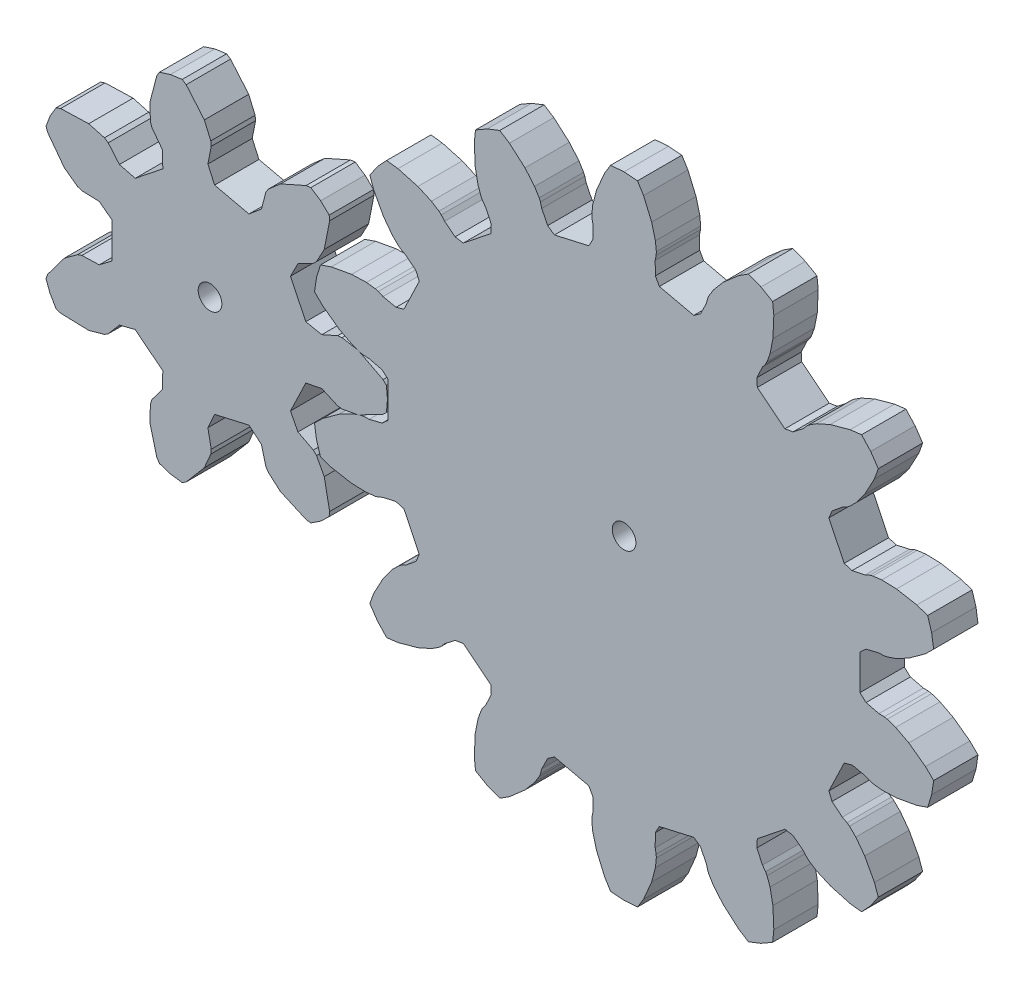
SolidWorks part; units mm, degrees
ref_plane "Front Plane" through (0, 0, 0) normal (0, 0, 1) x (1, 0, 0)
ref_plane "Top Plane" through (0, 0, 0) normal (0, 1, 0) x (1, 0, 0)
ref_plane "Right Plane" through (0, 0, 0) normal (1, 0, 0) x (0, 0, -1)
sketch "Model" plane through (0, 0, 0) normal (0, 0, 1) x (1, 0, 0)
  line L0 (10.824, -15.5893) -> (11.8775, -14.8939)
  line L1 (11.8775, -14.8939) -> (12.7899, -14.0216)
  line L2 (12.7899, -14.0216) -> (12.8434, -13.5144)
  line L3 (12.8434, -13.5144) -> (12.2623, -10.5576)
  line L4 (12.2623, -10.5576) -> (11.4342, -9.0171)
  line L5 (11.4342, -9.0171) -> (11.0892, -8.677)
  line L6 (11.0892, -8.677) -> (9.4401, -7.8202)
  line L7 (9.4401, -7.8202) -> (8.6391, -6.2612)
  line L8 (8.6391, -6.2612) -> (10.2816, -2.8505)
  line L9 (10.2816, -2.8505) -> (11.9999, -2.5047)
  line L10 (11.9999, -2.5047) -> (13.698, -3.2599)
  line L11 (13.698, -3.2599) -> (14.179, -3.3175)
  line L12 (14.179, -3.3175) -> (15.8632, -3.0111)
  line L13 (15.8632, -3.0111) -> (15.2951, -3.2054)
  line L14 (15.2951, -3.2054) -> (13.8858, -3.9376)
  line L15 (13.8858, -3.9376) -> (12.0928, -5.2415)
  line L16 (12.0928, -5.2415) -> (11.2168, -6.1052)
  line L17 (11.2168, -6.1052) -> (11.4324, -7.536)
  line L18 (11.4324, -7.536) -> (11.8589, -8.9187)
  line L19 (11.8589, -8.9187) -> (13.023, -9.3169)
  line L20 (13.023, -9.3169) -> (15.2041, -9.7136)
  line L21 (15.2041, -9.7136) -> (16.7916, -9.7618)
  line L22 (16.7916, -9.7618) -> (17.7443, -9.6477)
  line L23 (17.7443, -9.6477) -> (18.0633, -9.5598)
  line L24 (18.0633, -9.5598) -> (18.5734, -9.3329)
  line L25 (18.5734, -9.3329) -> (19.9687, -9.0348)
  line L26 (19.9687, -9.0348) -> (20.819, -9.2793)
  line L27 (20.819, -9.2793) -> (22.4615, -12.6899)
  line L28 (22.4615, -12.6899) -> (22.1225, -13.5071)
  line L29 (22.1225, -13.5071) -> (21.0194, -14.4122)
  line L30 (21.0194, -14.4122) -> (20.524, -14.6696)
  line L31 (20.524, -14.6696) -> (20.2564, -14.8641)
  line L32 (20.2564, -14.8641) -> (19.5731, -15.5378)
  line L33 (19.5731, -15.5378) -> (18.621, -16.809)
  line L34 (18.621, -16.809) -> (17.5714, -18.7617)
  line L35 (17.5714, -18.7617) -> (17.1569, -19.92)
  line L36 (17.1569, -19.92) -> (17.972, -21.1155)
  line L37 (17.972, -21.1155) -> (18.9562, -22.1762)
  line L38 (18.9562, -22.1762) -> (20.1777, -22.0299)
  line L39 (20.1777, -22.0299) -> (22.3149, -21.441)
  line L40 (22.3149, -21.441) -> (23.7661, -20.7956)
  line L41 (23.7661, -20.7956) -> (24.575, -20.2794)
  line L42 (24.575, -20.2794) -> (24.8242, -20.0619)
  line L43 (24.8242, -20.0619) -> (25.1854, -19.6361)
  line L44 (25.1854, -19.6361) -> (26.3132, -18.7621)
  line L45 (26.3132, -18.7621) -> (27.1854, -18.6134)
  line L46 (27.1854, -18.6134) -> (30.145, -20.9737)
  line L47 (30.145, -20.9737) -> (30.1941, -21.8571)
  line L48 (30.1941, -21.8571) -> (29.593, -23.151)
  line L49 (29.593, -23.151) -> (29.2583, -23.5979)
  line L50 (29.2583, -23.5979) -> (29.1016, -23.8893)
  line L51 (29.1016, -23.8893) -> (28.7783, -24.7928)
  line L52 (28.7783, -24.7928) -> (28.4721, -26.3512)
  line L53 (28.4721, -26.3512) -> (28.3736, -28.5659)
  line L54 (28.3736, -28.5659) -> (28.5027, -29.7893)
  line L55 (28.5027, -29.7893) -> (29.7558, -30.5128)
  line L56 (29.7558, -30.5128) -> (31.1028, -31.0414)
  line L57 (31.1028, -31.0414) -> (32.1398, -30.3796)
  line L58 (32.1398, -30.3796) -> (33.8099, -28.9217)
  line L59 (33.8099, -28.9217) -> (34.8374, -27.7106)
  line L60 (34.8374, -27.7106) -> (35.3421, -26.8946)
  line L61 (35.3421, -26.8946) -> (35.4723, -26.5904)
  line L62 (35.4723, -26.5904) -> (35.613, -26.0501)
  line L63 (35.613, -26.0501) -> (36.2499, -24.7734)
  line L64 (36.2499, -24.7734) -> (36.9712, -24.261)
  line L65 (36.9712, -24.261) -> (40.6618, -25.1033)
  line L66 (40.6618, -25.1033) -> (41.0893, -25.8779)
  line L67 (41.0893, -25.8779) -> (41.1092, -27.3046)
  line L68 (41.1092, -27.3046) -> (41.0015, -27.8524)
  line L69 (41.0015, -27.8524) -> (40.9868, -28.183)
  line L70 (40.9868, -28.183) -> (41.0875, -29.1372)
  line L71 (41.0875, -29.1372) -> (41.4877, -30.6741)
  line L72 (41.4877, -30.6741) -> (42.3599, -32.7123)
  line L73 (42.3599, -32.7123) -> (43.0071, -33.7585)
  line L74 (43.0071, -33.7585) -> (44.45, -33.8667)
  line L75 (44.45, -33.8667) -> (45.8929, -33.7585)
  line L76 (45.8929, -33.7585) -> (46.5401, -32.7123)
  line L77 (46.5401, -32.7123) -> (47.4123, -30.6741)
  line L78 (47.4123, -30.6741) -> (47.8125, -29.1372)
  line L79 (47.8125, -29.1372) -> (47.9132, -28.183)
  line L80 (47.9132, -28.183) -> (47.8985, -27.8524)
  line L81 (47.8985, -27.8524) -> (47.7908, -27.3046)
  line L82 (47.7908, -27.3046) -> (47.8107, -25.8779)
  line L83 (47.8107, -25.8779) -> (48.2382, -25.1033)
  line L84 (48.2382, -25.1033) -> (51.9288, -24.261)
  line L85 (51.9288, -24.261) -> (52.6501, -24.7734)
  line L86 (52.6501, -24.7734) -> (53.287, -26.0501)
  line L87 (53.287, -26.0501) -> (53.4277, -26.5904)
  line L88 (53.4277, -26.5904) -> (53.5579, -26.8946)
  line L89 (53.5579, -26.8946) -> (54.0626, -27.7106)
  line L90 (54.0626, -27.7106) -> (55.0901, -28.9217)
  line L91 (55.0901, -28.9217) -> (56.7602, -30.3796)
  line L92 (56.7602, -30.3796) -> (57.7972, -31.0414)
  line L93 (57.7972, -31.0414) -> (59.1442, -30.5128)
  line L94 (59.1442, -30.5128) -> (60.3973, -29.7893)
  line L95 (60.3973, -29.7893) -> (60.5264, -28.5659)
  line L96 (60.5264, -28.5659) -> (60.4279, -26.3512)
  line L97 (60.4279, -26.3512) -> (60.1217, -24.7928)
  line L98 (60.1217, -24.7928) -> (59.7984, -23.8893)
  line L99 (59.7984, -23.8893) -> (59.6417, -23.5979)
  line L100 (59.6417, -23.5979) -> (59.307, -23.151)
  line L101 (59.307, -23.151) -> (58.7059, -21.8571)
  line L102 (58.7059, -21.8571) -> (58.755, -20.9737)
  line L103 (58.755, -20.9737) -> (61.7146, -18.6134)
  line L104 (61.7146, -18.6134) -> (62.5868, -18.7621)
  line L105 (62.5868, -18.7621) -> (63.7146, -19.6361)
  line L106 (63.7146, -19.6361) -> (64.0758, -20.0619)
  line L107 (64.0758, -20.0619) -> (64.325, -20.2794)
  line L108 (64.325, -20.2794) -> (65.1339, -20.7956)
  line L109 (65.1339, -20.7956) -> (66.5851, -21.441)
  line L110 (66.5851, -21.441) -> (68.7223, -22.0299)
  line L111 (68.7223, -22.0299) -> (69.9438, -22.1762)
  line L112 (69.9438, -22.1762) -> (70.928, -21.1155)
  line L113 (70.928, -21.1155) -> (71.7431, -19.92)
  line L114 (71.7431, -19.92) -> (71.3286, -18.7617)
  line L115 (71.3286, -18.7617) -> (70.279, -16.809)
  line L116 (70.279, -16.809) -> (69.3269, -15.5378)
  line L117 (69.3269, -15.5378) -> (68.6436, -14.8641)
  line L118 (68.6436, -14.8641) -> (68.376, -14.6696)
  line L119 (68.376, -14.6696) -> (67.8806, -14.4122)
  line L120 (67.8806, -14.4122) -> (66.7775, -13.5071)
  line L121 (66.7775, -13.5071) -> (66.4385, -12.6899)
  line L122 (66.4385, -12.6899) -> (68.081, -9.2793)
  line L123 (68.081, -9.2793) -> (68.9313, -9.0348)
  line L124 (68.9313, -9.0348) -> (70.3266, -9.3329)
  line L125 (70.3266, -9.3329) -> (70.8367, -9.5598)
  line L126 (70.8367, -9.5598) -> (71.1557, -9.6477)
  line L127 (71.1557, -9.6477) -> (72.1084, -9.7618)
  line L128 (72.1084, -9.7618) -> (73.6959, -9.7136)
  line L129 (73.6959, -9.7136) -> (75.877, -9.3169)
  line L130 (75.877, -9.3169) -> (77.0411, -8.9187)
  line L131 (77.0411, -8.9187) -> (77.4676, -7.536)
  line L132 (77.4676, -7.536) -> (77.6832, -6.1052)
  line L133 (77.6832, -6.1052) -> (76.8072, -5.2415)
  line L134 (76.8072, -5.2415) -> (75.0142, -3.9376)
  line L135 (75.0142, -3.9376) -> (73.6049, -3.2054)
  line L136 (73.6049, -3.2054) -> (72.697, -2.8949)
  line L137 (72.697, -2.8949) -> (72.3715, -2.8357)
  line L138 (72.3715, -2.8357) -> (71.8134, -2.8188)
  line L139 (71.8134, -2.8188) -> (70.4269, -2.482)
  line L140 (70.4269, -2.482) -> (69.7669, -1.8928)
  line L141 (69.7669, -1.8928) -> (69.7669, 1.8928)
  line L142 (69.7669, 1.8928) -> (70.4269, 2.482)
  line L143 (70.4269, 2.482) -> (71.8134, 2.8188)
  line L144 (71.8134, 2.8188) -> (72.3715, 2.8357)
  line L145 (72.3715, 2.8357) -> (72.697, 2.8949)
  line L146 (72.697, 2.8949) -> (73.6049, 3.2054)
  line L147 (73.6049, 3.2054) -> (75.0142, 3.9376)
  line L148 (75.0142, 3.9376) -> (76.8072, 5.2415)
  line L149 (76.8072, 5.2415) -> (77.6832, 6.1052)
  line L150 (77.6832, 6.1052) -> (77.4676, 7.536)
  line L151 (77.4676, 7.536) -> (77.0411, 8.9187)
  line L152 (77.0411, 8.9187) -> (75.877, 9.3169)
  line L153 (75.877, 9.3169) -> (73.6959, 9.7136)
  line L154 (73.6959, 9.7136) -> (72.1084, 9.7618)
  line L155 (72.1084, 9.7618) -> (71.1557, 9.6477)
  line L156 (71.1557, 9.6477) -> (70.8367, 9.5598)
  line L157 (70.8367, 9.5598) -> (70.3266, 9.3329)
  line L158 (70.3266, 9.3329) -> (68.9313, 9.0348)
  line L159 (68.9313, 9.0348) -> (68.081, 9.2793)
  line L160 (68.081, 9.2793) -> (66.4385, 12.6899)
  line L161 (66.4385, 12.6899) -> (66.7775, 13.5071)
  line L162 (66.7775, 13.5071) -> (67.8806, 14.4122)
  line L163 (67.8806, 14.4122) -> (68.376, 14.6696)
  line L164 (68.376, 14.6696) -> (68.6436, 14.8641)
  line L165 (68.6436, 14.8641) -> (69.3269, 15.5378)
  line L166 (69.3269, 15.5378) -> (70.279, 16.809)
  line L167 (70.279, 16.809) -> (71.3286, 18.7617)
  line L168 (71.3286, 18.7617) -> (71.7431, 19.92)
  line L169 (71.7431, 19.92) -> (70.928, 21.1155)
  line L170 (70.928, 21.1155) -> (69.9438, 22.1762)
  line L171 (69.9438, 22.1762) -> (68.7223, 22.0299)
  line L172 (68.7223, 22.0299) -> (66.5851, 21.441)
  line L173 (66.5851, 21.441) -> (65.1339, 20.7956)
  line L174 (65.1339, 20.7956) -> (64.325, 20.2794)
  line L175 (64.325, 20.2794) -> (64.0758, 20.0619)
  line L176 (64.0758, 20.0619) -> (63.7146, 19.6361)
  line L177 (63.7146, 19.6361) -> (62.5868, 18.7621)
  line L178 (62.5868, 18.7621) -> (61.7146, 18.6134)
  line L179 (61.7146, 18.6134) -> (58.755, 20.9737)
  line L180 (58.755, 20.9737) -> (58.7059, 21.8571)
  line L181 (58.7059, 21.8571) -> (59.307, 23.151)
  line L182 (59.307, 23.151) -> (59.6417, 23.5979)
  line L183 (59.6417, 23.5979) -> (59.7984, 23.8893)
  line L184 (59.7984, 23.8893) -> (60.1217, 24.7928)
  line L185 (60.1217, 24.7928) -> (60.4279, 26.3512)
  line L186 (60.4279, 26.3512) -> (60.5264, 28.5659)
  line L187 (60.5264, 28.5659) -> (60.3973, 29.7893)
  line L188 (60.3973, 29.7893) -> (59.1442, 30.5128)
  line L189 (59.1442, 30.5128) -> (57.7972, 31.0414)
  line L190 (57.7972, 31.0414) -> (56.7602, 30.3796)
  line L191 (56.7602, 30.3796) -> (55.0901, 28.9217)
  line L192 (55.0901, 28.9217) -> (54.0626, 27.7106)
  line L193 (54.0626, 27.7106) -> (53.5579, 26.8946)
  line L194 (53.5579, 26.8946) -> (53.4277, 26.5904)
  line L195 (53.4277, 26.5904) -> (53.287, 26.0501)
  line L196 (53.287, 26.0501) -> (52.6501, 24.7734)
  line L197 (52.6501, 24.7734) -> (51.9288, 24.261)
  line L198 (51.9288, 24.261) -> (48.2382, 25.1033)
  line L199 (48.2382, 25.1033) -> (47.8107, 25.8779)
  line L200 (47.8107, 25.8779) -> (47.7908, 27.3046)
  line L201 (47.7908, 27.3046) -> (47.8985, 27.8524)
  line L202 (47.8985, 27.8524) -> (47.9132, 28.183)
  line L203 (47.9132, 28.183) -> (47.8125, 29.1372)
  line L204 (47.8125, 29.1372) -> (47.4123, 30.6741)
  line L205 (47.4123, 30.6741) -> (46.5401, 32.7123)
  line L206 (46.5401, 32.7123) -> (45.8929, 33.7585)
  line L207 (45.8929, 33.7585) -> (44.45, 33.8667)
  line L208 (44.45, 33.8667) -> (43.0071, 33.7585)
  line L209 (43.0071, 33.7585) -> (42.3599, 32.7123)
  line L210 (42.3599, 32.7123) -> (41.4877, 30.6741)
  line L211 (41.4877, 30.6741) -> (41.0875, 29.1372)
  line L212 (41.0875, 29.1372) -> (40.9868, 28.183)
  line L213 (40.9868, 28.183) -> (41.0015, 27.8524)
  line L214 (41.0015, 27.8524) -> (41.1092, 27.3046)
  line L215 (41.1092, 27.3046) -> (41.0893, 25.8779)
  line L216 (41.0893, 25.8779) -> (40.6618, 25.1033)
  line L217 (40.6618, 25.1033) -> (36.9712, 24.261)
  line L218 (36.9712, 24.261) -> (36.2499, 24.7734)
  line L219 (36.2499, 24.7734) -> (35.613, 26.0501)
  line L220 (35.613, 26.0501) -> (35.4723, 26.5904)
  line L221 (35.4723, 26.5904) -> (35.3421, 26.8946)
  line L222 (35.3421, 26.8946) -> (34.8374, 27.7106)
  line L223 (34.8374, 27.7106) -> (33.8099, 28.9217)
  line L224 (33.8099, 28.9217) -> (32.1398, 30.3796)
  line L225 (32.1398, 30.3796) -> (31.1028, 31.0414)
  line L226 (31.1028, 31.0414) -> (29.7558, 30.5128)
  line L227 (29.7558, 30.5128) -> (28.5027, 29.7893)
  line L228 (28.5027, 29.7893) -> (28.3736, 28.5659)
  line L229 (28.3736, 28.5659) -> (28.4721, 26.3512)
  line L230 (28.4721, 26.3512) -> (28.7783, 24.7928)
  line L231 (28.7783, 24.7928) -> (29.1016, 23.8893)
  line L232 (29.1016, 23.8893) -> (29.2583, 23.5979)
  line L233 (29.2583, 23.5979) -> (29.593, 23.151)
  line L234 (29.593, 23.151) -> (30.1941, 21.8571)
  line L235 (30.1941, 21.8571) -> (30.145, 20.9737)
  line L236 (30.145, 20.9737) -> (27.1854, 18.6134)
  line L237 (27.1854, 18.6134) -> (26.3132, 18.7621)
  line L238 (26.3132, 18.7621) -> (25.1854, 19.6361)
  line L239 (25.1854, 19.6361) -> (24.8242, 20.0619)
  line L240 (24.8242, 20.0619) -> (24.575, 20.2794)
  line L241 (24.575, 20.2794) -> (23.7661, 20.7956)
  line L242 (23.7661, 20.7956) -> (22.3149, 21.441)
  line L243 (22.3149, 21.441) -> (20.1777, 22.0299)
  line L244 (20.1777, 22.0299) -> (18.9562, 22.1762)
  line L245 (18.9562, 22.1762) -> (17.972, 21.1155)
  line L246 (17.972, 21.1155) -> (17.1569, 19.92)
  line L247 (17.1569, 19.92) -> (17.5714, 18.7617)
  line L248 (17.5714, 18.7617) -> (18.621, 16.809)
  line L249 (18.621, 16.809) -> (19.5731, 15.5378)
  line L250 (19.5731, 15.5378) -> (20.2564, 14.8641)
  line L251 (20.2564, 14.8641) -> (20.524, 14.6696)
  line L252 (20.524, 14.6696) -> (21.0194, 14.4122)
  line L253 (21.0194, 14.4122) -> (22.1225, 13.5071)
  line L254 (22.1225, 13.5071) -> (22.4615, 12.6899)
  line L255 (22.4615, 12.6899) -> (20.819, 9.2793)
  line L256 (20.819, 9.2793) -> (19.9687, 9.0348)
  line L257 (19.9687, 9.0348) -> (18.5734, 9.3329)
  line L258 (18.5734, 9.3329) -> (18.0633, 9.5598)
  line L259 (18.0633, 9.5598) -> (17.7443, 9.6477)
  line L260 (17.7443, 9.6477) -> (16.7916, 9.7618)
  line L261 (16.7916, 9.7618) -> (15.2041, 9.7136)
  line L262 (15.2041, 9.7136) -> (13.023, 9.3169)
  line L263 (13.023, 9.3169) -> (11.8589, 8.9187)
  line L264 (11.8589, 8.9187) -> (11.4324, 7.536)
  line L265 (11.4324, 7.536) -> (11.2168, 6.1052)
  line L266 (11.2168, 6.1052) -> (12.0928, 5.2415)
  line L267 (12.0928, 5.2415) -> (13.8858, 3.9376)
  line L268 (13.8858, 3.9376) -> (15.2951, 3.2054)
  line L269 (15.2951, 3.2054) -> (15.8632, 3.0111)
  line L270 (15.8632, 3.0111) -> (14.179, 3.3175)
  line L271 (14.179, 3.3175) -> (13.698, 3.2599)
  line L272 (13.698, 3.2599) -> (11.9999, 2.5047)
  line L273 (11.9999, 2.5047) -> (10.2816, 2.8505)
  line L274 (10.2816, 2.8505) -> (8.6391, 6.2612)
  line L275 (8.6391, 6.2612) -> (9.4401, 7.8202)
  line L276 (9.4401, 7.8202) -> (11.0892, 8.677)
  line L277 (11.0892, 8.677) -> (11.4342, 9.0171)
  line L278 (11.4342, 9.0171) -> (12.2623, 10.5576)
  line L279 (12.2623, 10.5576) -> (12.8434, 13.5144)
  line L280 (12.8434, 13.5144) -> (12.7899, 14.0216)
  line L281 (12.7899, 14.0216) -> (11.8775, 14.8939)
  line L282 (11.8775, 14.8939) -> (10.824, 15.5893)
  line L283 (10.824, 15.5893) -> (10.3177, 15.5286)
  line L284 (10.3177, 15.5286) -> (7.5643, 14.3042)
  line L285 (7.5643, 14.3042) -> (6.2467, 13.154)
  line L286 (6.2467, 13.154) -> (5.9919, 12.742)
  line L287 (5.9919, 12.742) -> (5.5235, 10.9436)
  line L288 (5.5235, 10.9436) -> (4.1818, 9.8158)
  line L289 (4.1818, 9.8158) -> (0.4912, 10.6581)
  line L290 (0.4912, 10.6581) -> (-0.2283, 12.2564)
  line L291 (-0.2283, 12.2564) -> (0.1301, 14.0799)
  line L292 (0.1301, 14.0799) -> (0.0792, 14.5617)
  line L293 (0.0792, 14.5617) -> (-0.6088, 16.1696)
  line L294 (-0.6088, 16.1696) -> (-2.5583, 18.4675)
  line L295 (-2.5583, 18.4675) -> (-2.9881, 18.7418)
  line L296 (-2.9881, 18.7418) -> (-4.239, 18.5724)
  line L297 (-4.239, 18.5724) -> (-5.4396, 18.1823)
  line L298 (-5.4396, 18.1823) -> (-5.7078, 17.7486)
  line L299 (-5.7078, 17.7486) -> (-6.4672, 14.8325)
  line L300 (-6.4672, 14.8325) -> (-6.3895, 13.0853)
  line L301 (-6.3895, 13.0853) -> (-6.2262, 12.6291)
  line L302 (-6.2262, 12.6291) -> (-5.1122, 11.1417)
  line L303 (-5.1122, 11.1417) -> (-5.067, 9.3895)
  line L304 (-5.067, 9.3895) -> (-8.0266, 7.0293)
  line L305 (-8.0266, 7.0293) -> (-9.7248, 7.4633)
  line L306 (-9.7248, 7.4633) -> (-10.927, 8.8804)
  line L307 (-10.927, 8.8804) -> (-11.3354, 9.141)
  line L308 (-11.3354, 9.141) -> (-13.0215, 9.6056)
  line L309 (-13.0215, 9.6056) -> (-16.0335, 9.5141)
  line L310 (-16.0335, 9.5141) -> (-16.516, 9.3491)
  line L311 (-16.516, 9.3491) -> (-17.1635, 8.2655)
  line L312 (-17.1635, 8.2655) -> (-17.607, 7.0837)
  line L313 (-17.607, 7.0837) -> (-17.4352, 6.6035)
  line L314 (-17.4352, 6.6035) -> (-15.6287, 4.1916)
  line L315 (-15.6287, 4.1916) -> (-14.2142, 3.163)
  line L316 (-14.2142, 3.163) -> (-13.7559, 3.0063)
  line L317 (-13.7559, 3.0063) -> (-11.8983, 2.9499)
  line L318 (-11.8983, 2.9499) -> (-10.5002, 1.8928)
  line L319 (-10.5002, 1.8928) -> (-10.5002, -1.8928)
  line L320 (-10.5002, -1.8928) -> (-11.8983, -2.9499)
  line L321 (-11.8983, -2.9499) -> (-13.7559, -3.0063)
  line L322 (-13.7559, -3.0063) -> (-14.2142, -3.163)
  line L323 (-14.2142, -3.163) -> (-15.6287, -4.1916)
  line L324 (-15.6287, -4.1916) -> (-17.4352, -6.6035)
  line L325 (-17.4352, -6.6035) -> (-17.607, -7.0837)
  line L326 (-17.607, -7.0837) -> (-17.1635, -8.2655)
  line L327 (-17.1635, -8.2655) -> (-16.516, -9.3491)
  line L328 (-16.516, -9.3491) -> (-16.0335, -9.5141)
  line L329 (-16.0335, -9.5141) -> (-13.0215, -9.6056)
  line L330 (-13.0215, -9.6056) -> (-11.3354, -9.141)
  line L331 (-11.3354, -9.141) -> (-10.927, -8.8804)
  line L332 (-10.927, -8.8804) -> (-9.7248, -7.4633)
  line L333 (-9.7248, -7.4633) -> (-8.0266, -7.0293)
  line L334 (-8.0266, -7.0293) -> (-5.067, -9.3895)
  line L335 (-5.067, -9.3895) -> (-5.1122, -11.1417)
  line L336 (-5.1122, -11.1417) -> (-6.2262, -12.6291)
  line L337 (-6.2262, -12.6291) -> (-6.3895, -13.0853)
  line L338 (-6.3895, -13.0853) -> (-6.4672, -14.8325)
  line L339 (-6.4672, -14.8325) -> (-5.7078, -17.7486)
  line L340 (-5.7078, -17.7486) -> (-5.4396, -18.1823)
  line L341 (-5.4396, -18.1823) -> (-4.239, -18.5724)
  line L342 (-4.239, -18.5724) -> (-2.9881, -18.7418)
  line L343 (-2.9881, -18.7418) -> (-2.5583, -18.4675)
  line L344 (-2.5583, -18.4675) -> (-0.6088, -16.1696)
  line L345 (-0.6088, -16.1696) -> (0.0792, -14.5617)
  line L346 (0.0792, -14.5617) -> (0.1301, -14.0799)
  line L347 (0.1301, -14.0799) -> (-0.2283, -12.2564)
  line L348 (-0.2283, -12.2564) -> (0.4912, -10.6581)
  line L349 (0.4912, -10.6581) -> (4.1818, -9.8158)
  line L350 (4.1818, -9.8158) -> (5.5235, -10.9436)
  line L351 (5.5235, -10.9436) -> (5.9919, -12.742)
  line L352 (5.9919, -12.742) -> (6.2467, -13.154)
  line L353 (6.2467, -13.154) -> (7.5643, -14.3042)
  line L354 (7.5643, -14.3042) -> (10.3177, -15.5286)
  line L355 (10.3177, -15.5286) -> (10.824, -15.5893)
  line L356 (15.9326, -2.9874) -> (18.5737, -1.6153)
  line L357 (18.5737, -1.6153) -> (18.9368, -1.2572)
  line L358 (18.9368, -1.2572) -> (19.05, 0)
  line L359 (19.05, 0) -> (18.9368, 1.2572)
  line L360 (18.9368, 1.2572) -> (18.5737, 1.6153)
  line L361 (18.5737, 1.6153) -> (15.9326, 2.9874)
  line L362 (15.9326, 2.9874) -> (16.203, 2.8949)
  line L363 (16.203, 2.8949) -> (16.5285, 2.8357)
  line L364 (16.5285, 2.8357) -> (17.0866, 2.8188)
  line L365 (17.0866, 2.8188) -> (18.4731, 2.482)
  line L366 (18.4731, 2.482) -> (19.1331, 1.8928)
  line L367 (19.1331, 1.8928) -> (19.1331, -1.8928)
  line L368 (19.1331, -1.8928) -> (18.4731, -2.482)
  line L369 (18.4731, -2.482) -> (17.0866, -2.8188)
  line L370 (17.0866, -2.8188) -> (16.5285, -2.8357)
  line L371 (16.5285, -2.8357) -> (16.203, -2.8949)
  line L372 (16.203, -2.8949) -> (15.9326, -2.9874)
  line L435 (15.8632, 3.0111) -> (15.9326, 2.9874)
  line L436 (15.9326, -2.9874) -> (15.8632, -3.0111)
  circle A0 centre (0, 0) radius 1.27
  circle A1 centre (44.45, 0) radius 1.27
  point P433 (44.45, 0)
  dimension "D2" = 2.54
  dimension "D3" = 2.54
  dimension "D1" = 44.45
extrude "Boss-Extrude2" add sketch "Model" along normal blind 4.7625 contours L436 L356 L357 L358 L359 L360 L361 L435 L270 L271 L272 L273 L274 L275 L276 L277 L278 L279 L280 L281 L282 L283 L284 L285 L286 L287 L288 L289 L290 L291 L292 L293 L294 L295 L296 L297 L298 L299 L300 L301 L302 L303 L304 L305 L306 L307 L308 L309 L310 L311 L312 region at (10.6332, -15.0384, 0)
extrude "Boss-Extrude3" add sketch "Model<4>" along normal blind 4.7625 separate body contours L372 L436 L13 L14 L15 L16 L17 L18 L19 L20 L21 L22 L23 L24 L25 L26 L27 L28 L29 L30 L31 L32 L33 L34 L35 L36 L37 L38 L39 L40 L41 L42 L43 L44 L45 L46 L47 L48 L49 L50 L51 L52 L53 L54 L55 L56 L57 L58 L59 L60 L61 region at (16.205, -3.8972, 0)
sketch "Model<4>" plane through (0, 0, 0) normal (0, 0, 1) x (1, 0, 0) same geometry as "Model"
